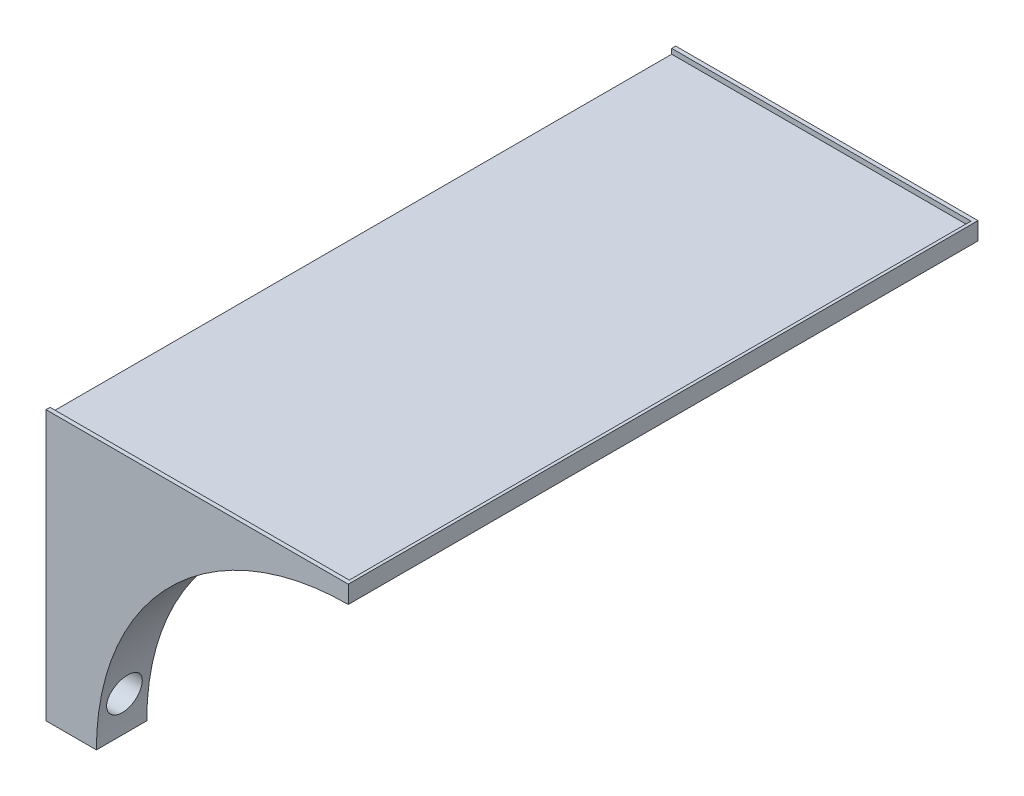
SolidWorks part; units mm, degrees
ref_plane "Přední rovina" through (0, 0, 0) normal (0, 0, 1) x (1, 0, 0)
ref_plane "Horní rovina" through (0, 0, 0) normal (0, 1, 0) x (1, 0, 0)
ref_plane "Pravá rovina" through (0, 0, 0) normal (1, 0, 0) x (0, 0, -1)
sketch "Skica1" plane through (0, 0, 0) normal (0, 0, 1) x (1, 0, 0)
  line L0 (0, 0) -> (0, 105)
  line L1 (0, 105) -> (120, 105)
  line L2 (120, 105) -> (120, 100)
  line L3 (0, 0) -> (20, 0)
  arc A0 (20, 0) -> (120, 100) centre (120, 0) cw
  point P3 (0, 0)
  dimension "D1" = 120
  dimension "D2" = 105
  dimension "D3" = 20
  dimension "D4" = 5
extrude "Přidat vysunutím1" add sketch "Skica1" along normal blind 250
sketch "Skica2" plane through (0, 0, 0) normal (0, -1, 0) x (1, 0, 0)
  line L0 (0, 250) -> (0, 0) construction
  line L1 (0, 230) -> (120, 230)
  line L2 (0, 230) -> (0, 20)
  line L3 (0, 20) -> (120, 20)
  line L4 (120, 230) -> (120, 20)
  dimension "D1" = 20
  dimension "D2" = 20
  dimension "D3" = 120
extrude "Odebrat vysunutím1" cut sketch "Skica2" against normal blind 100
sketch "Skica3" plane through (120, 0, 0) normal (-1, 0, 0) x (0, 0, 1)
  line L0 (240, 0) -> (240, 105)
  line L1 (250, 0) -> (230, 0) construction
  line L2 (250, 105) -> (0, 105) construction
  point P6 (240, 15)
  point P7 (240, 91)
  dimension "D1" = 76
  dimension "D2" = 15
hole_wizard "Válcové zahloubení pro M6 šrouby s válcovou hlavou zaoblenou1" positions "Skica6" profile "Skica7" counterbore size "M6" standard "ANSI Metric" end condition through all
sketch "Skica6" plane through (120, 0, 0) normal (1, 0, 0) x (0, 0, -1)
  point P0 (-240, 91)
  point P3 (-240, 15)
sketch "Skica7" plane through (120, 91, 240) normal (0, 1, 0) x (0, 0, -1)
  line L0 (0, 0) -> (0, 120)
  line L1 (0, 120) -> (3.3, 120)
  line L3 (3.3, 120) -> (3.3, 115)
  line L4 (3.3, 115) -> (7, 115)
  line L5 (7, 115) -> (7, 0)
  line L7 (7, 0) -> (0, 0)
  line L11 (0, -6.35) -> (0, 107.95) construction
  dimension "Průměr díry skrz" = 6.6
  dimension "Hloubka díry skrz" = 120
  dimension "Průměr válcového zahloubení" = 14
  dimension "Hloubka válcového zahloubení" = 115
ref_plane "Rovina1" through (0, 0, 125) normal (0, 0, 1) x (1, 0, 0)
mirror "Zrcadlit1" about plane through (0, 0, 125) normal (0, 0, 1) of "Válcové zahloubení pro M6 šrouby s válcovou hlavou zaoblenou1"
sketch "Skica8" plane through (0, 105, 0) normal (0, 1, 0) x (1, 0, 0)
  line L0 (0, 0) -> (120, 0)
  line L1 (120, 0) -> (120, -250)
  line L2 (120, -250) -> (0, -250)
  line L3 (0, -250) -> (0, -248.4)
  line L4 (0, -250) -> (0, 0) construction
  line L5 (0, -248.4) -> (116.8, -248.4)
  line L6 (116.8, -248.4) -> (116.8, -1.6)
  line L7 (116.8, -1.6) -> (0, -1.6)
  line L8 (0, -1.6) -> (0, 0)
  dimension "D1" = 1.6
  dimension "D2" = 3.2
extrude "Přidat vysunutím2" add sketch "Skica8" along normal blind 2
chamfer "Zkosení1" distance 2 angle 45 1 edges at (116.8, 107, 125)
